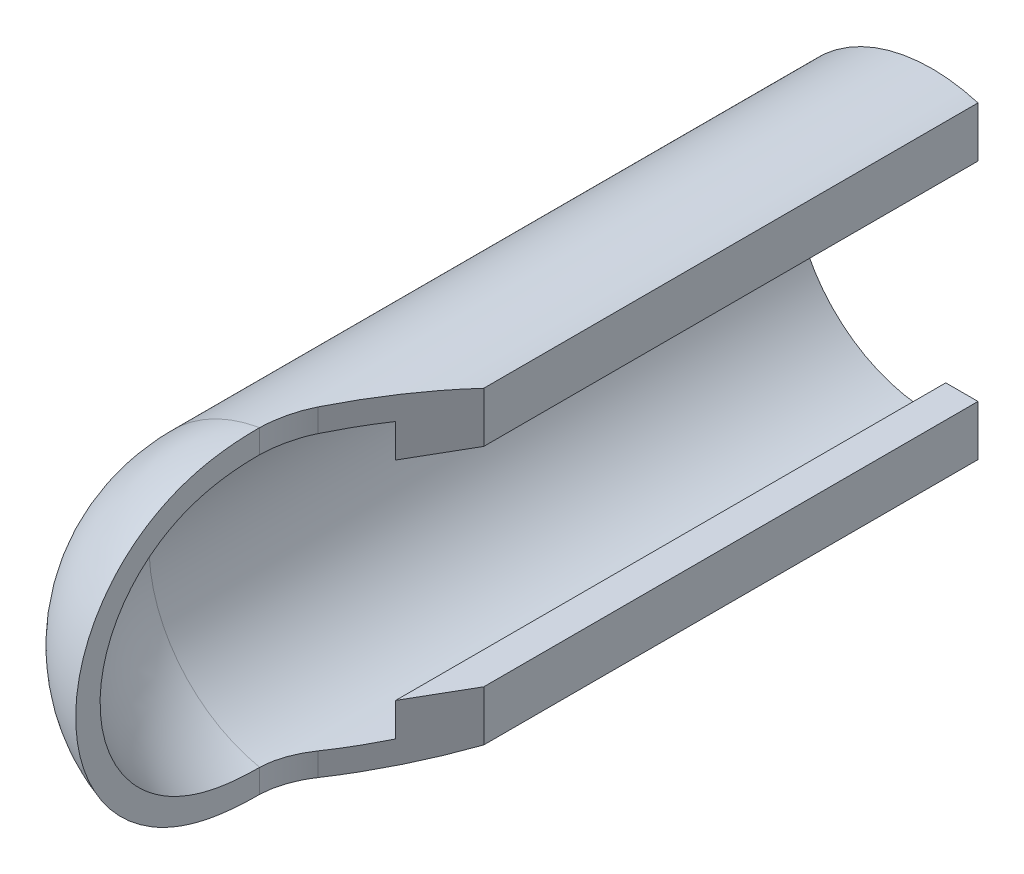
SolidWorks part; units mm, degrees
ref_plane "Front Plane" through (0, 0, 0) normal (0, 0, 1) x (1, 0, 0)
ref_plane "Top Plane" through (0, 0, 0) normal (0, 1, 0) x (1, 0, 0)
ref_plane "Right Plane" through (0, 0, 0) normal (1, 0, 0) x (0, 0, -1)
sketch "Sketch1" plane through (0, 0, 0) normal (0, 0, 1) x (1, 0, 0)
  line L3 (10, 33.541) -> (10, 22.6)
  line L4 (10, 22.6) -> (3, 22.6)
  line L5 (3, 22.6) -> (3, 29.8496)
  line L6 (10, 0) -> (-35, 0) construction
  line L7 (10, -33.541) -> (10, -22.6)
  line L8 (10, -22.6) -> (3, -22.6)
  line L9 (3, -22.6) -> (3, -29.8496)
  arc A0 (10, 33.541) -> (10, -33.541) centre (0, 0) ccw
  arc A2 (3, 29.8496) -> (3, -29.8496) centre (0, 0) ccw
  circle A4 centre (0, 0) radius 35 construction
  circle A5 centre (0, 0) radius 30 construction
  point P1 (14.995, 13.5)
  point P2 (0, 0)
  point P9 (18.4657, 23.733)
  dimension "D1" = 70
  dimension "D3" = 10
  dimension "D4" = 45.2
  dimension "D5" = 3
  dimension "D2" = 5
extrude "Boss-Extrude1" add sketch "Sketch1" against normal blind 140
ref_plane "Plane1" through (0, 35, 0) normal (0, 1, 0) x (1, 0, 0)
sketch "Sketch2" plane through (0, 35, 0) normal (0, 1, 0) x (1, 0, 0)
  line L0 (10, 32.6811) -> (-3.1815, 9.85)
  line L1 (10, 140) -> (10, 0) construction
  line L2 (10, 32.6811) -> (10, 0)
  line L3 (10, 0) -> (-5.9849, 0)
  arc A0 (-3.1815, 9.85) -> (-5.9849, 0) centre (15.005, -0.65) ccw
  arc A1 (15.7777, 19.3351) -> (14.2323, -20.6351) centre (15.005, -0.65) ccw construction
  dimension "D1" = 1
  dimension "D2" = 30
extrude "Cut-Extrude1" cut sketch "Sketch2" against normal through all
sketch "Sketch6" plane through (0, 0, 0) normal (0, 0, 1) x (1, 0, 0)
  line L2 (7, 34.2929) -> (7, -34.2929) construction
  line L4 (-5.9849, 29.3969) -> (-5.9849, 34.4845)
  line L5 (-5.9849, -34.4845) -> (-5.9849, -29.3969)
  line L6 (-5.9849, 29.3969) -> (-5.9849, 34.4845)
  line L7 (-5.9849, -34.4845) -> (-5.9849, -29.3969)
  arc A4 (-5.9849, 34.4845) -> (-5.9849, -34.4845) centre (0, 0) ccw
  arc A5 (-5.9849, 29.3969) -> (-5.9849, -29.3969) centre (0, 0) ccw
  arc A6 (-5.9849, 34.4845) -> (-5.9849, -34.4845) centre (0, 0) ccw
  arc A7 (-5.9849, 29.3969) -> (-5.9849, -29.3969) centre (0, 0) ccw
  point P2 (0, 0)
  point P4 (0, 0)
  point P6 (-35, 0)
  dimension "D2" = 42
  dimension "D1" = 0
revolve "Revolve1" add sketch "Sketch6" angle 90 about L2 reverse direction yes
ref_plane "Plane2" through (0, 0, 0) normal (0, 0, -1) x (-1, 0, 0)
sketch "Sketch7" plane through (0, 0, 0) normal (0, 0, -1) x (-1, 0, 0)
  line L0 (5.9849, 34.4845) -> (-7, 34.4845)
  line L3 (-7, 29.3969) -> (-7, -29.3969) construction
  line L6 (-7, -40) -> (-7, 34.4845)
  line L7 (5.9849, -35.134) -> (-7, -40)
  line L8 (5.9849, 34.4845) -> (5.9849, -35.134)
  arc A0 (-10, -33.541) -> (-10, 33.541) centre (0, 0) ccw construction
  point P3 (5, 13.5)
  point P5 (-28, 33)
  point P6 (-28, 12.4717)
  point P7 (0, 0)
  point P9 (4.995, 33.5)
extrude "Cut-Extrude2" cut sketch "Sketch7" against normal through all
